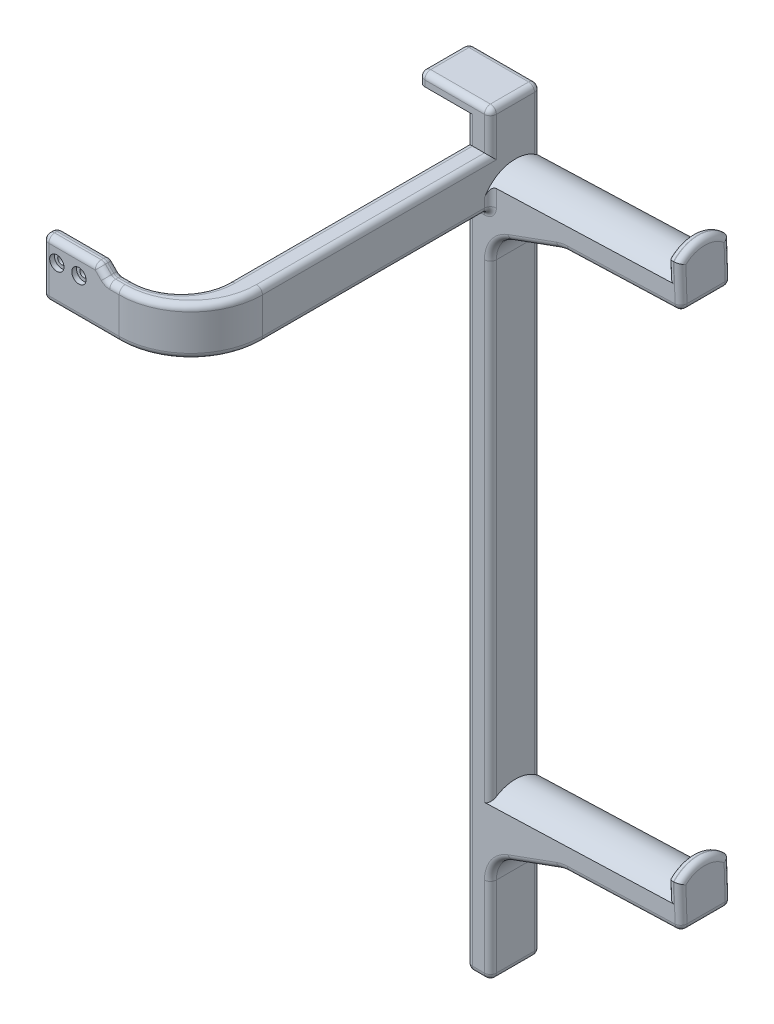
SolidWorks part; units mm, degrees
ref_plane "Front Plane" through (0, 0, 0) normal (0, 0, 1) x (1, 0, 0)
ref_plane "Top Plane" through (0, 0, 0) normal (0, 1, 0) x (1, 0, 0)
ref_plane "Right Plane" through (0, 0, 0) normal (1, 0, 0) x (0, 0, -1)
sketch "Sketch2" plane through (0, 0, 0) normal (0, 0, 1) x (1, 0, 0)
  line L0 (-4.625, 0) -> (4.625, 0) construction
  line L1 (-10.5, -16) -> (10.5, -16)
  line L2 (-10.5, -16) -> (-10.5, 8)
  line L3 (-10.5, 8) -> (10.5, 8)
  line L4 (10.5, -16) -> (10.5, 8)
  line L5 (0, 8) -> (0, -16) construction
  circle A0 centre (-4.625, 0) radius 1.625
  circle A1 centre (4.625, 0) radius 1.625
  point P0 (0, 0)
  point P8 (0, 0)
  dimension "D3" = 3.25
  dimension "D1" = 21
  dimension "D2" = 9.25
  dimension "D4" = 8
  dimension "D5" = 16
extrude "Boss-Extrude1" add sketch "Sketch2" against normal blind 6
sketch "Sketch4" plane through (0, 0, 0) normal (0, 0, 1) x (1, 0, 0)
  line L4 (41.5, 4) -> (41.5, -16)
  line L7 (41.5, 4) -> (10.5, 4)
  line L8 (10.5, -16) -> (10.5, 8) construction
  line L9 (10.5, 4) -> (10.5, -16)
  line L10 (10.5, -16) -> (41.5, -16)
  dimension "D1" = 20
  dimension "D4" = 41.5
extrude "Boss-Extrude3" add sketch "Sketch4" against normal up to surface (6 mm away) up to face at (6.25, 0, -6)
sketch "Sketch5" plane through (41.5, 0, 0) normal (1, 0, 0) x (0, 0, -1)
  line L0 (6, -16) -> (6, 4) construction
  line L1 (0, 4) -> (136, 4)
  line L2 (0, 4) -> (0, -16)
  line L3 (0, -16) -> (136, -16)
  line L4 (136, 4) -> (136, -16) construction
  line L5 (136, 4) -> (146.5, 4)
  line L6 (146.5, 4) -> (146.5, -16)
  line L7 (146.5, -16) -> (136, -16)
  dimension "D1" = 130
  dimension "D2" = 10.5
extrude "Boss-Extrude4" add sketch "Sketch5" along normal blind 10
fillet "Fillet3" radius 20 1 edges at (41.5, -6, -6)
fillet "Fillet4" radius 30 1 edges at (51.5, -6, 0)
sketch "Sketch9" plane through (0, 4, 0) normal (0, 1, 0) x (1, 0, 0)
  line L0 (41.5, 146.5) -> (41.5, 26) construction
  line L1 (51.5, 146.5) -> (41.5, 146.5)
  line L2 (51.5, 146.5) -> (51.5, 125.5)
  line L3 (51.5, 125.5) -> (41.5, 125.5)
  line L4 (41.5, 146.5) -> (41.5, 125.5)
  dimension "D1" = 21
extrude "Boss-Extrude7" add sketch "Sketch9" along normal blind 11.5 and the other way blind 300
ref_plane "Plane11" through (50.8792, 1.7767, 0) normal (0.9994, 0.0349, 0) x (0, 0, -1)
sketch "Sketch7" plane through (50.9707, -0.8427, 0) normal (0.9994, 0.0349, 0) x (0, 0, -1)
  line L1 (146.5, -15.1665) -> (125.5, -15.1665)
  line L2 (146.5, -15.1665) -> (146.5, -5.6665)
  line L4 (125.5, -15.1665) -> (125.5, -5.6665)
  arc A0 (125.5, -5.6665) -> (146.5, -5.6665) centre (136, -16.1665) cw
  dimension "D1" = 21
  dimension "D2" = 9.5
extrude "Boss-Extrude9" add sketch "Sketch7" along normal blind 80
sketch "Sketch8" plane through (130.9068, 2.3821, 0) normal (0.9994, 0.0349, 0) x (0, 0, -1)
  line L0 (146.5, -15.5996) -> (125.5, -15.5996)
  line L1 (125.5, -15.5996) -> (125.5, 1.9004)
  line L2 (146.5, -15.5996) -> (146.5, 1.9004)
  arc A0 (125.5, 1.9004) -> (146.5, 1.9004) centre (136, -8.5996) cw
  dimension "D1" = 17.5
extrude "Boss-Extrude6" add sketch "Sketch8" against normal blind 5.2
pattern_linear "LPattern1" count 2 spacing 225 along (0, -1, 0) of "Boss-Extrude9", "Boss-Extrude6"
sketch "Sketch10" plane through (0, 15.5, 0) normal (0, 1, 0) x (1, 0, 0)
  line L0 (41.5, 125.5) -> (41.5, 146.5) construction
  line L1 (51.5, 146.5) -> (21.5, 146.5)
  line L2 (51.5, 146.5) -> (51.5, 125.5)
  line L3 (51.5, 125.5) -> (21.5, 125.5)
  line L4 (21.5, 146.5) -> (21.5, 125.5)
  dimension "D1" = 20
extrude "Boss-Extrude8" add sketch "Sketch10" along normal blind 5
chamfer "Chamfer1" distance 6 angle 45 1 edges at (10.5, 4, -3)
chamfer "Chamfer2" distance 10 angle 70 2 edges at (51.5, -16, -136) (51.5, -241, -136)
fillet "Fillet2" radius 12.5 4 edges at (51.5, -26, -136) (81.8906, -14.9387, -136) (51.5, -251, -136) (81.8906, -239.9387, -136)
fillet "Fillet1" radius 2.5 74 edges at (130.6887, 8.6279, -136) (125.7833, 0.1023, -146.5) (125.7833, 0.1023, -125.5) (125.4919, 8.4464, -136) (-10.5, -4, -6) (51.5, -133.1234, -125.5) (51.5, -133.1234, -146.5) (51.5, -227.1423, -136) (107.6602, -239.0388, -146.5) (107.6602, -239.0388, -125.5) (131.1459, -229.4634, -146.5) (131.1459, -229.4634, -125.5) (131.4513, -238.208, -136) (130.6887, -216.3721, -136) (125.7833, -224.8977, -146.5) (125.7833, -224.8977, -125.5) (125.4919, -216.5536, -136) (5.5, -16, -6) (21.5, 18, -146.5) (21.5, 18, -125.5) (51.5, 20.5, -136) (36.5, 20.5, -146.5) (21.5, 20.5, -136) (36.5, 20.5, -125.5) (16.5, 4, -3) (14.5, 6, 0) (12.5, 8, -3) (14.5, 6, -6) (69.8775, -244.3112, -125.5) (69.8775, -244.3112, -146.5) (69.8775, -19.3112, -125.5) (69.8775, -19.3112, -146.5) (53.7606, -252.5829, -125.5) (53.7606, -252.5829, -146.5) (81.9203, -240.0917, -146.5) (81.9203, -240.0917, -125.5) (53.7606, -27.5829, -125.5) (53.7606, -27.5829, -146.5) (81.9203, -15.0917, -146.5) (81.9203, -15.0917, -125.5) (41.5, -140.25, -146.5) (51.5, -277.8763, -146.5) (5.5, -16, 0) (41.5, -16, -75.75) (19, 4, -6) (35.6421, 4, -11.8579) (-10.5, -4, 0) (35.6421, -16, -11.8579) (1, 8, 0) (51.5, -16, -77.75) (42.7132, -16, -8.7868) (19, 4, 0) (42.7132, 4, -8.7868) (51.5, 4, -77.75) (41.5, 4, -75.75) (51.5, -296, -136) (41.5, -156, -125.5) (41.5, -296, -136) (51.5, -277.8763, -125.5) (46.5, -16, -125.5) (46.5, -296, -125.5) (46.5, -296, -146.5) (51.5, 12.25, -125.5) (41.5, 9.75, -125.5) (-10.5, -16, -3) (-10.5, 8, -3) (1, 8, -6) (51.5, 7.0029, -146.5) (51.5, -11.2471, -125.5) (107.6602, -14.0388, -146.5) (107.6602, -14.0388, -125.5) (131.1459, -4.4634, -146.5) (131.1459, -4.4634, -125.5) (131.4513, -13.208, -136)
sketch "Sketch12" plane through (0, 0, 0) normal (0, 0, 1) x (1, 0, 0)
  circle A0 centre (-4.625, 0) radius 3
  circle A1 centre (4.625, 0) radius 3
  dimension "D1" = 6
extrude "Cut-Extrude2" cut sketch "Sketch12" against normal blind 2
ref_plane "Plane12" through (0, -100, 0) normal (0, 1, 0) x (1, 0, 0)
